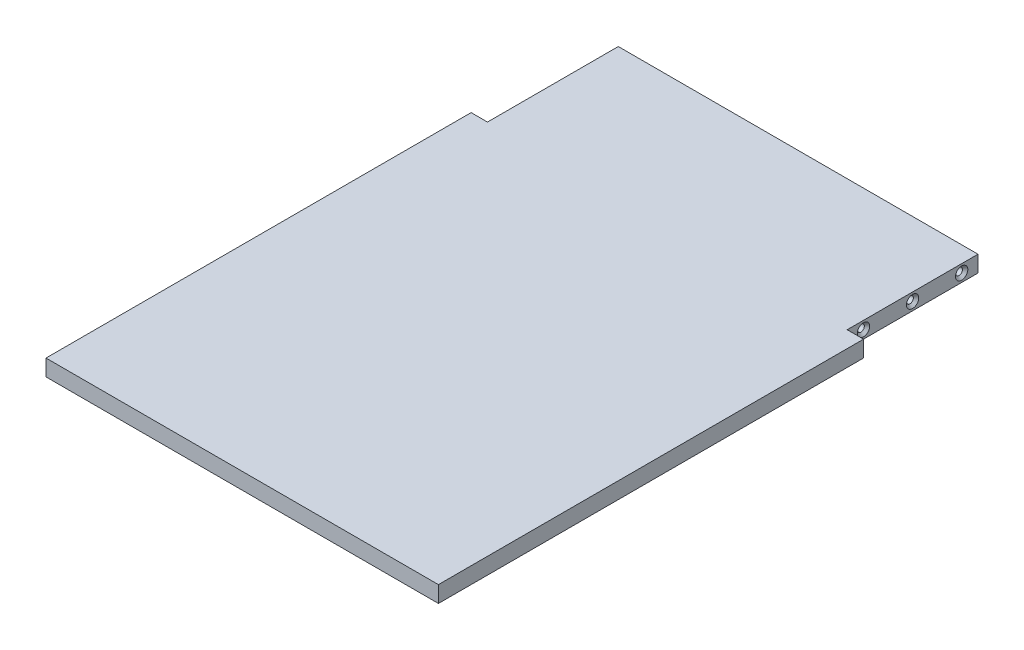
SolidWorks part; units mm, degrees
ref_plane "Front Plane" through (0, 0, 0) normal (0, 0, 1) x (1, 0, 0)
ref_plane "Top Plane" through (0, 0, 0) normal (0, 1, 0) x (1, 0, 0)
ref_plane "Right Plane" through (0, 0, 0) normal (1, 0, 0) x (0, 0, -1)
sketch "Sketch1" plane through (0, 0, 0) normal (0, 1, 0) x (1, 0, 0)
  line L0 (-6.35, 0) -> (-6.35, -50.8)
  line L1 (-6.35, 0) -> (-146.05, 0)
  line L2 (0, -50.8) -> (0, -215.9)
  line L3 (0, -215.9) -> (-152.4, -215.9)
  line L4 (-152.4, -50.8) -> (-152.4, -215.9)
  line L5 (-6.35, -50.8) -> (0, -50.8)
  line L6 (-146.05, 0) -> (-146.05, -50.8)
  line L7 (-146.05, -50.8) -> (-152.4, -50.8)
  point P7 (-3.175, -50.8)
  dimension "D1" = 152.4
  dimension "D2" = 215.9
  dimension "D3" = 50.8
  dimension "D4" = 6.35
  dimension "D5" = 6.35
  dimension "D6" = 50.8
extrude "Boss-Extrude1" add sketch "Sketch1" along normal blind 6.35
sketch "Sketch2" plane through (-6.35, 0, 0) normal (1, 0, 0) x (0, 0, -1)
  line L0 (-50.8, 6.35) -> (-50.8, 0) construction
  line L1 (-50.8, 6.35) -> (-50.8, 0) construction
  line L2 (-50.8, 0) -> (0, 0) construction
  circle A0 centre (-44.45, 3.175) radius 1.8288
  circle A1 centre (-25.4, 3.175) radius 1.8288
  circle A2 centre (-6.35, 3.175) radius 1.8288
  dimension "D4" = 3.175
  dimension "D5" = 3.175
  dimension "D6" = 3.6576
  dimension "D7" = 3.6576
  dimension "D8" = 3.6576
  dimension "D1" = 6.35
  dimension "D2" = 25.4
  dimension "D3" = 44.45
hole_wizard "#6-32 Tapped Hole1" positions "Sketch3" profile "Sketch4" tap size "#6-32" standard "ANSI Inch"
sketch "Sketch3" plane through (-6.35, 0, 0) normal (1, 0, 0) x (0, 0, -1)
  point P0 (-44.45, 3.175)
  point P3 (-25.4, 3.175)
  point P6 (-6.35, 3.175)
sketch "Sketch4" plane through (-6.35, 3.175, 44.45) normal (0, 1, 0) x (0, 0, -1)
  line L0 (0, 0) -> (0, 12.7)
  line L1 (0, 12.7) -> (1.3525, 11.8873)
  line L2 (1.3525, 11.8873) -> (1.3525, 1.0351)
  line L3 (1.3525, 1.0351) -> (2.3876, 0)
  line L5 (2.3876, 0) -> (0, 0)
  line L6 (-1.3525, 1.0351) -> (-2.3876, 0) construction
  line L10 (0, 12.7) -> (-1.3526, 11.8873) construction
  line L11 (0, -6.35) -> (0, 107.95) construction
  dimension "Tap Drill Dia." = 2.7051
  dimension "Tap Drill Depth" = 12.7
  dimension "Near C'Sink Dia." = 4.7752
  dimension "Near C'Sink Angle" = 90
  dimension "Drill Angle" = 118
cosmetic thread "Hole Thread1"
cosmetic thread "Hole Thread2"
cosmetic thread "Hole Thread3"
sketch "Sketch5" plane through (-146.05, 0, 0) normal (-1, 0, 0) x (0, 0, 1)
  circle A0 centre (6.35, 3.175) radius 1.8288
  circle A1 centre (25.4, 3.175) radius 1.8288
  circle A2 centre (44.45, 3.175) radius 1.8288
  dimension "D1" = 3.6576
  dimension "D2" = 3.6576
  dimension "D3" = 3.6576
hole_wizard "#6-32 Tapped Hole2" positions "Sketch6" profile "Sketch7" tap size "#6-32" standard "ANSI Inch"
sketch "Sketch6" plane through (-146.05, 0, 0) normal (-1, 0, 0) x (0, 0, 1)
  point P0 (6.35, 3.175)
  point P3 (25.4, 3.175)
  point P6 (44.45, 3.175)
sketch "Sketch7" plane through (-146.05, 3.175, 6.35) normal (0, 1, 0) x (0, 0, 1)
  line L0 (0, 0) -> (0, 12.7)
  line L1 (0, 12.7) -> (1.3525, 11.8873)
  line L2 (1.3525, 11.8873) -> (1.3525, 1.0351)
  line L3 (1.3525, 1.0351) -> (2.3876, 0)
  line L5 (2.3876, 0) -> (0, 0)
  line L6 (-1.3525, 1.0351) -> (-2.3876, 0) construction
  line L10 (0, 12.7) -> (-1.3526, 11.8873) construction
  line L11 (0, -6.35) -> (0, 107.95) construction
  dimension "Tap Drill Dia." = 2.7051
  dimension "Tap Drill Depth" = 12.7
  dimension "Near C'Sink Dia." = 4.7752
  dimension "Near C'Sink Angle" = 90
  dimension "Drill Angle" = 118
cosmetic thread "Hole Thread4"
cosmetic thread "Hole Thread5"
cosmetic thread "Hole Thread6"
